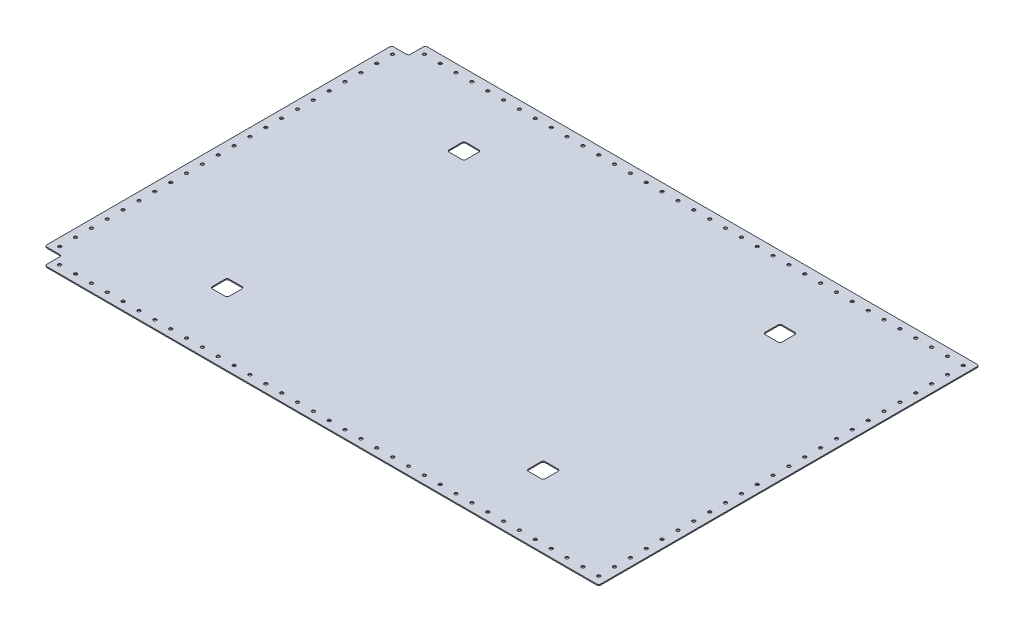
SolidWorks part; units mm, degrees
material "6061-T6 (SS)"
ref_plane "Front Plane" through (0, 0, 0) normal (0, 0, 1) x (1, 0, 0)
ref_plane "Top Plane" through (0, 0, 0) normal (0, 1, 0) x (1, 0, 0)
ref_plane "Right Plane" through (0, 0, 0) normal (1, 0, 0) x (0, 0, -1)
sketch "Sketch1" plane through (0, 0, 0) normal (0, 1, 0) x (1, 0, 0)
  line L1 (457.2, -304.8) -> (-457.2, -304.8)
  line L2 (457.2, -304.8) -> (457.2, 304.8)
  line L3 (457.2, 304.8) -> (-457.2, 304.8)
  line L4 (-457.2, -304.8) -> (-457.2, 304.8)
  line L5 (457.2, -304.8) -> (-457.2, 304.8) construction
  line L6 (457.2, 304.8) -> (-457.2, -304.8) construction
  line L7 (-457.2, 304.8) -> (-430.2125, 304.8)
  line L8 (-457.2, 304.8) -> (-457.2, 277.8125)
  line L9 (-457.2, 277.8125) -> (-430.2125, 277.8125)
  line L10 (-430.2125, 304.8) -> (-430.2125, 277.8125)
  line L11 (-457.2, -304.8) -> (-430.2125, -304.8)
  line L12 (-457.2, -304.8) -> (-457.2, -277.8125)
  line L13 (-457.2, -277.8125) -> (-430.2125, -277.8125)
  line L14 (-430.2125, -304.8) -> (-430.2125, -277.8125)
  point P0 (0, 0)
  dimension "D1" = 609.6
  dimension "D2" = 914.4
  dimension "D3" = 26.9875
extrude "Boss-Extrude1" add sketch "Sketch1" along normal blind 1.5875 contours L14 L1 L2 L3 L10 L9 L4 L13 region at (1.1625, 0, 0)
sketch "Sketch2" plane through (0, 1.5875, 0) normal (0, 1, 0) x (1, 0, 0)
  line L0 (457.2, 304.8) -> (-430.2125, 304.8) construction
  line L1 (457.2, -304.8) -> (457.2, 304.8) construction
  circle A0 centre (444.5, 292.1) radius 2.4892
  dimension "D3" = 4.9784
  dimension "D1" = 12.7
  dimension "D2" = 12.7
extrude "Cut-Extrude1" cut sketch "Sketch2" against normal through all
pattern_linear "LPattern1" count 24 spacing 25.4 along (0, 0, 1) count 35 spacing 25.4 along (-1, 0, 0) of "Cut-Extrude1" pattern seed only yes
pattern_linear "LPattern2" count 35 spacing 25.4 along (-1, 0, 0) of face at (444.5, 0, 294.5892)
sketch "Sketch3" plane through (0, 1.5875, 0) normal (0, 1, 0) x (1, 0, 0)
  line L0 (-457.2, 277.8125) -> (-430.2125, 277.8125) construction
  line L1 (-457.2, -277.8125) -> (-457.2, 277.8125) construction
  circle A0 centre (-444.5, 266.7) radius 2.4892
  circle A1 centre (-419.1, 292.1) radius 2.4892 construction
  dimension "D1" = 11.1125
  dimension "D2" = 12.7
extrude "Cut-Extrude2" cut sketch "Sketch3" against normal through all
pattern_linear "LPattern3" count 22 spacing 25.4 along (0, 0, 1) of "Cut-Extrude2"
sketch "Sketch4" plane through (0, 1.5875, 0) normal (0, 1, 0) x (1, 0, 0)
  line L0 (-457.2, -277.8125) -> (-457.2, 277.8125) construction
  line L1 (-266.7, 203.2) -> (-239.7125, 203.2)
  line L2 (-266.7, 203.2) -> (-266.7, 176.2125)
  line L3 (-266.7, 176.2125) -> (-239.7125, 176.2125)
  line L4 (-239.7125, 203.2) -> (-239.7125, 176.2125)
  line L5 (-266.7, -176.2125) -> (-239.7125, -176.2125)
  line L6 (-266.7, -176.2125) -> (-266.7, -203.2)
  line L7 (-266.7, -203.2) -> (-239.7125, -203.2)
  line L8 (-239.7125, -176.2125) -> (-239.7125, -203.2)
  line L9 (239.7125, 203.2) -> (266.7, 203.2)
  line L10 (239.7125, 203.2) -> (239.7125, 176.2125)
  line L11 (239.7125, 176.2125) -> (266.7, 176.2125)
  line L12 (266.7, 203.2) -> (266.7, 176.2125)
  line L13 (239.7125, -176.2125) -> (266.7, -176.2125)
  line L14 (239.7125, -176.2125) -> (239.7125, -203.2)
  line L15 (239.7125, -203.2) -> (266.7, -203.2)
  line L16 (266.7, -176.2125) -> (266.7, -203.2)
  line L17 (457.2, -304.8) -> (457.2, 304.8) construction
  line L18 (457.2, 304.8) -> (-430.2125, 304.8) construction
  line L19 (457.2, -304.8) -> (-430.2125, -304.8) construction
  point P16 (-266.7, 189.7063)
  dimension "D1" = 26.9875
  dimension "D2" = 190.5
  dimension "D3" = 190.5
  dimension "D4" = 101.6
  dimension "D5" = 101.6
extrude "Cut-Extrude3" cut sketch "Sketch4" against normal through all
fillet "Fillet1" radius 3.175 24 edges at (-430.2125, 0.7937, 277.8125) (-457.2, 0.7937, 277.8125) (-457.2, 0.7937, -277.8125) (-430.2125, 0.7937, -277.8125) (457.2, 0.7937, -304.8) (457.2, 0.7937, 304.8) (-430.2125, 0.7937, 304.8) (-266.7, 0.7937, -176.2125) (-239.7125, 0.7937, -176.2125) (-239.7125, 0.7937, -203.2) (-266.7, 0.7937, -203.2) (239.7125, 0.7937, 203.2) (266.7, 0.7937, 203.2) (266.7, 0.7937, 176.2125) (239.7125, 0.7937, 176.2125) (239.7125, 0.7937, -176.2125) (266.7, 0.7937, -176.2125) (266.7, 0.7937, -203.2) (239.7125, 0.7937, -203.2) (-266.7, 0.7937, 203.2) (-239.7125, 0.7937, 203.2) (-239.7125, 0.7937, 176.2125) (-266.7, 0.7937, 176.2125) (-430.2125, 0.7937, -304.8)
